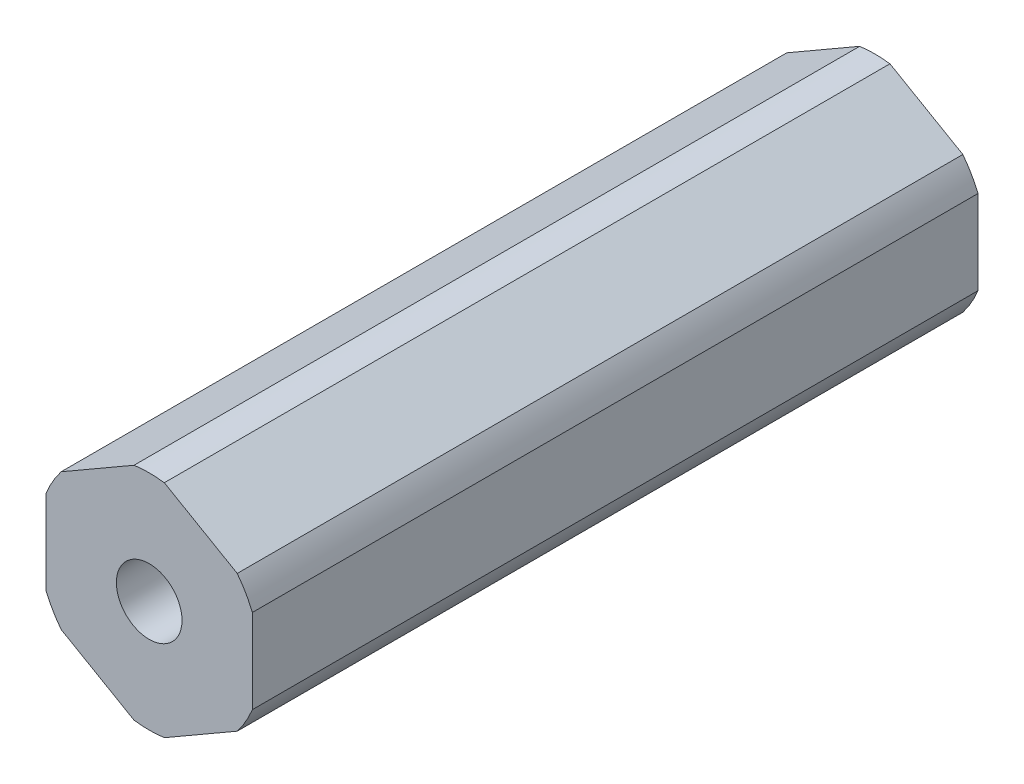
SolidWorks part; units mm, degrees
ref_plane "Front Plane" through (0, 0, 0) normal (0, 0, 1) x (1, 0, 0)
ref_plane "Top Plane" through (0, 0, 0) normal (0, 1, 0) x (1, 0, 0)
ref_plane "Right Plane" through (0, 0, 0) normal (1, 0, 0) x (0, 0, -1)
sketch "Sketch1" plane through (0, 0, 0) normal (0, 0, 1) x (1, 0, 0)
  line L1 (0, 7.3323) -> (-6.35, 3.6662)
  line L2 (-6.35, 3.6662) -> (-6.35, -3.6662)
  line L3 (-6.35, -3.6662) -> (0, -7.3323)
  line L4 (0, -7.3323) -> (6.35, -3.6662)
  line L5 (6.35, -3.6662) -> (6.35, 3.6662)
  line L6 (6.35, 3.6662) -> (0, 7.3323)
  circle A0 centre (0, 0) radius 6.35 construction
  circle A1 centre (0, 0) radius 6.858
  dimension "D1" = 12.7
  dimension "D2" = 13.716
extrude "Boss-Extrude1" add sketch "Sketch1" along normal mid plane 44.6532 contours L5 A1 L6 L1 L2 L3 L4 region at (0, 0, 0)
sketch "Sketch2" plane through (0, 0, 22.3266) normal (0, 0, 1) x (1, 0, 0)
  circle A0 centre (0, 0) radius 2.0193
  dimension "D1" = 4.0386
extrude "Cut-Extrude1" [suppressed] cut sketch "Sketch2" against normal through all
hole_wizard "#10-32 Tapped Hole2" positions "3DSketch4" profile "Sketch6" tap size "#10-32" standard "ANSI Inch"
sketch3d "3DSketch4"
  line L0 (0, 0, 22.3266) -> (0, 0, -22.3266) construction
  line L1 (0, 0, 22.3266) -> (0, 0, -22.3266) construction
  point P0 (0, 0, -22.3266)
  point P4 (0, 0, 22.3266)
sketch "Sketch6" plane through (0, 0, -22.3266) normal (1, 0, 0) x (0, 1, 0)
  line L0 (0, 0) -> (0, 13.2428)
  line L1 (0, 13.2428) -> (2.0193, 12.0294)
  line L2 (2.0193, 12.0294) -> (2.0193, 0)
  line L5 (2.0193, 0) -> (0, 0)
  line L10 (0, 13.2428) -> (-2.0193, 12.0294) construction
  line L11 (0, -6.35) -> (0, 107.95) construction
  dimension "Tap Drill Dia." = 4.0386
  dimension "Tap Drill Depth" = 12.0294
  dimension "Drill Angle" = 118
cosmetic thread "Hole Thread3" parameters "D1"=9.652, "D2"=4.826
cosmetic thread "Hole Thread4" parameters "D1"=9.652, "D2"=4.826
